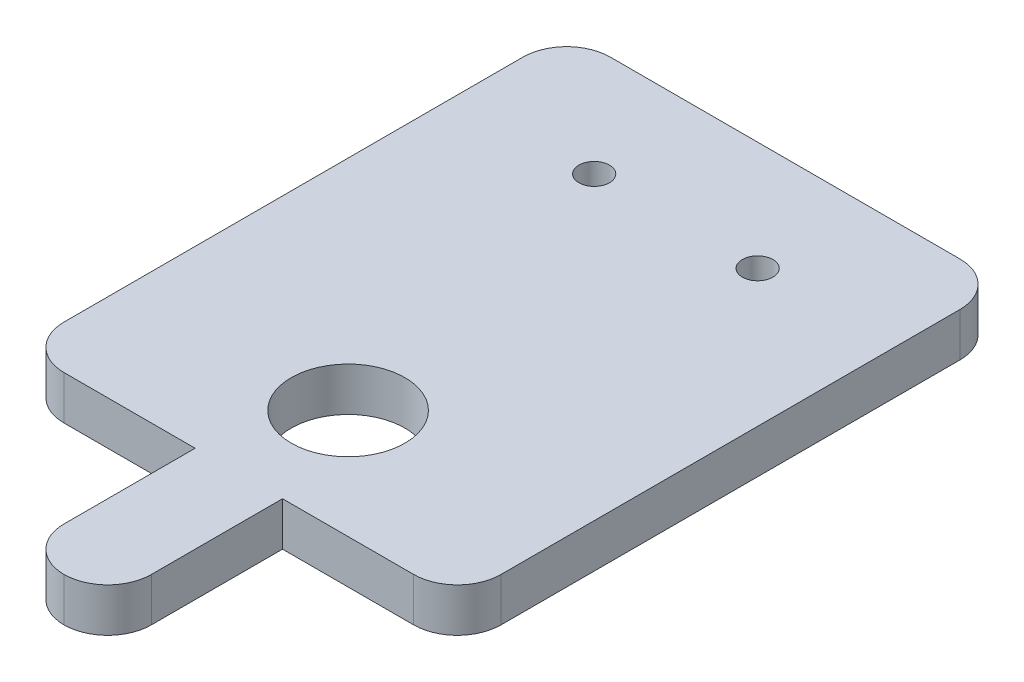
SolidWorks part; units mm, degrees
ref_plane "Front Plane" through (0, 0, 0) normal (0, 0, 1) x (1, 0, 0)
ref_plane "Top Plane" through (0, 0, 0) normal (0, 1, 0) x (1, 0, 0)
ref_plane "Right Plane" through (0, 0, 0) normal (1, 0, 0) x (0, 0, -1)
sketch "Sketch2" plane through (0, 0, 0) normal (0, 1, 0) x (1, 0, 0)
  line L1 (-6.8943, 7.1664) -> (18.5057, 7.1664)
  line L2 (-6.8943, 7.1664) -> (-6.8943, -24.5836)
  line L3 (-6.8943, -24.5836) -> (18.5057, -24.5836)
  line L4 (18.5057, 7.1664) -> (18.5057, -24.5836)
  dimension "D1" = 25.4
  dimension "D2" = 31.75
extrude "Boss-Extrude1" add sketch "Sketch2" along normal blind 2.54
hole_wizard "#50 (0.07) Diameter Hole1" positions "Sketch7" profile "Sketch6" hole size "#50" standard "ANSI Inch" end condition up to next
sketch "Sketch7" plane through (0, 2.54, 0) normal (0, 1, 0) x (1, 0, 0)
  line L0 (1.0557, 0.8164) -> (-6.8943, 0.8164)
  line L1 (-6.8943, 7.1664) -> (-6.8943, -24.5836) construction
  line L3 (10.5557, 0.8164) -> (18.5057, 0.8164)
  line L4 (18.5057, -24.5836) -> (18.5057, 7.1664) construction
  line L5 (18.5057, 7.1664) -> (-6.8943, 7.1664) construction
  point P0 (1.0557, 0.8164)
  point P2 (10.5557, 0.8164)
  dimension "D1" = 9.5
  dimension "D2" = 6.35
sketch "Sketch6" plane through (1.0557, 2.54, -0.8164) normal (1, 0, 0) x (0, 0, 1)
  line L0 (0, 0) -> (0, 2.54)
  line L1 (0, 2.54) -> (0.889, 2.54)
  line L2 (0.889, 2.54) -> (0.889, 0)
  line L5 (0.889, 0) -> (0, 0)
  line L11 (0, -6.35) -> (0, 107.95) construction
  dimension "Thru Hole Dia." = 1.778
  dimension "Thru Hole Depth" = 2.54
sketch "Sketch10" plane through (0, 2.54, 0) normal (0, 1, 0) x (1, 0, 0)
  line L0 (5.8057, -18.2336) -> (5.8057, -24.5836)
  line L1 (-6.8943, -24.5836) -> (18.5057, -24.5836) construction
  circle A0 centre (5.8057, -18.2336) radius 3.302
  dimension "D1" = 6.35
  dimension "D2" = 6.604
extrude "Cut-Extrude1" cut sketch "Sketch10" against normal blind 3.175 contours A0 region at (8.0745, 2.54, 20.5024)
sketch "Sketch11" plane through (0, 0, 24.5836) normal (0, 0, 1) x (1, 0, 0)
  line L0 (-6.8943, 0) -> (18.5057, 0) construction
  line L1 (3.2657, 0) -> (8.3457, 0)
  line L2 (3.2657, 0) -> (3.2657, 2.54)
  line L3 (3.2657, 2.54) -> (8.3457, 2.54)
  line L4 (8.3457, 0) -> (8.3457, 2.54)
  line L5 (-6.8943, 2.54) -> (18.5057, 2.54) construction
  line L6 (5.8057, 2.54) -> (5.8057, 0) construction
  dimension "D1" = 5.08
extrude "Boss-Extrude2" add sketch "Sketch11" along normal blind 10.16
fillet "Fillet1" radius 2.54 6 edges at (8.3457, 1.27, 34.7436) (3.2657, 1.27, 34.7436) (18.5057, 1.27, -7.1664) (18.5057, 1.27, 24.5836) (-6.8943, 1.27, 24.5836) (-6.8943, 1.27, -7.1664)
